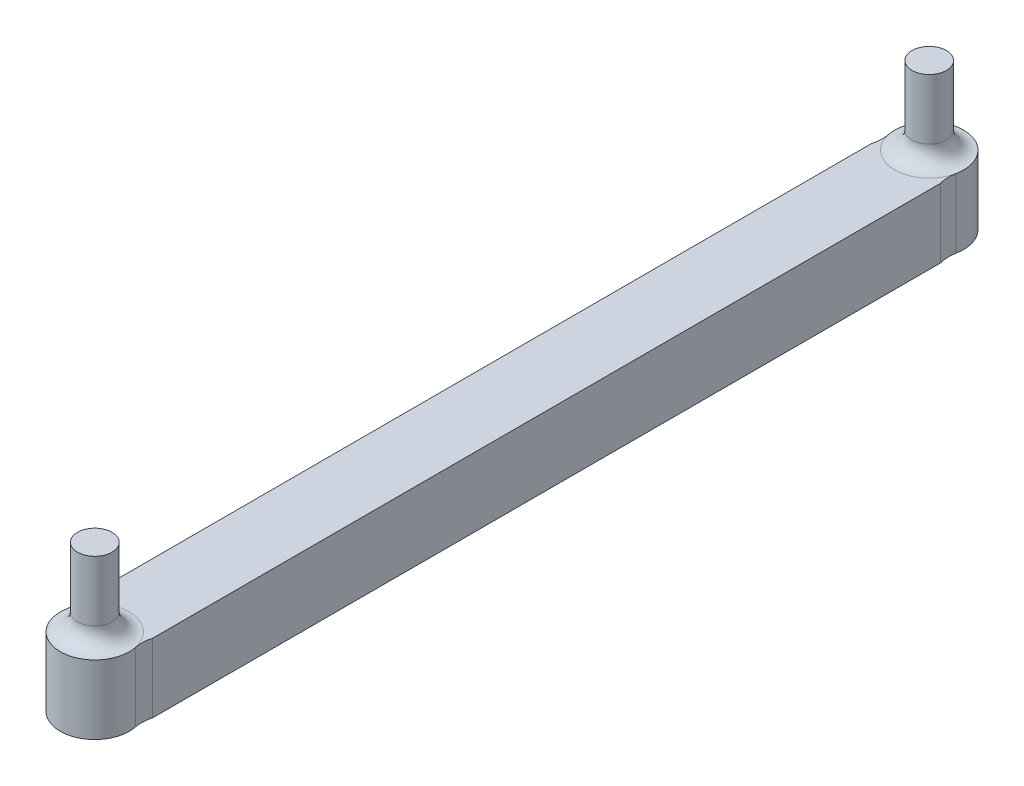
SolidWorks part; units mm, degrees
ref_plane "Ebene vorne" through (0, 0, 0) normal (0, 0, 1) x (1, 0, 0)
ref_plane "Ebene oben" through (0, 0, 0) normal (0, 1, 0) x (1, 0, 0)
ref_plane "Ebene rechts" through (0, 0, 0) normal (1, 0, 0) x (0, 0, -1)
sketch "Skizze1" plane through (0, 0, 0) normal (0, 0, 1) x (1, 0, 0)
  line L1 (-2, 2) -> (2, 2)
  line L2 (-2, 2) -> (-2, -2)
  line L3 (-2, -2) -> (2, -2)
  line L4 (2, 2) -> (2, -2)
  line L5 (-2, 2) -> (2, -2) construction
  line L6 (-2, -2) -> (2, 2) construction
  point P0 (0, 0)
  dimension "D1" = 4
  dimension "D2" = 4
extrude "Aufsatz-Linear austragen1" add sketch "Skizze1" along normal blind 45.7
sketch "Skizze2" plane through (0, 0, 0) normal (0, 1, 0) x (1, 0, 0)
  line L0 (0, -45.7) -> (0, 0) construction
  line L1 (2, -45.7) -> (-2, -45.7) construction
  circle A0 centre (0, -47.05) radius 2
  circle A2 centre (0, 1.35) radius 2
  point P9 (0, -22.85)
  dimension "D1" = 24.2
  dimension "D2" = 24.2
extrude "Aufsatz-Linear austragen2" add sketch "Skizze2" against normal blind 4 from offset 2
sketch "Skizze3" plane through (0, 2, 0) normal (0, 1, 0) x (1, 0, 0)
  circle A0 centre (0, -47.05) radius 1
  circle A2 centre (0, 1.35) radius 1
extrude "Aufsatz-Linear austragen4" add sketch "Skizze3" along normal blind 4.5
fillet "Verrundung1" radius 2 4 edges at (-1.4756, 0, 45.7) (1.4756, 0, 45.7) (-1.4756, 0, 0) (1.4756, 0, 0)
fillet "Verrundung2" radius 1 2 edges at (0, 2, -2.35) (0, 2, 46.05)
